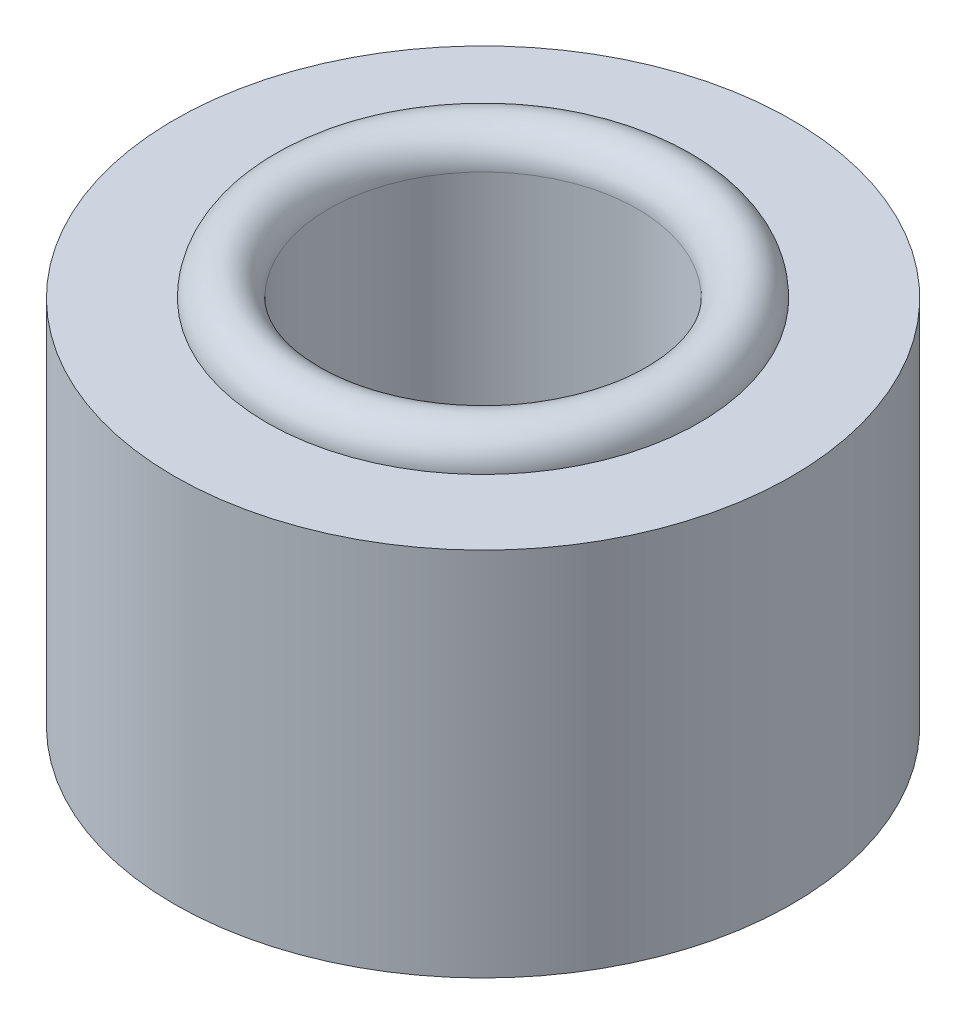
SolidWorks part; units mm, degrees
ref_plane "Front Plane" through (0, 0, 0) normal (0, 0, 1) x (1, 0, 0)
ref_plane "Top Plane" through (0, 0, 0) normal (0, 1, 0) x (1, 0, 0)
ref_plane "Right Plane" through (0, 0, 0) normal (1, 0, 0) x (0, 0, -1)
sketch "Profile Sketch" plane through (0, 0, 0) normal (0, 1, 0) x (1, 0, 0)
  circle A0 centre (0, 0) radius 10
  circle A1 centre (0, 0) radius 5
  dimension "D1" = 20
  dimension "D2" = 10
extrude "Cylinder Extrude" add sketch "Profile Sketch" along normal blind 12
sketch "Lip Ring Sketch" plane through (0, 12, 0) normal (0, 1, 0) x (1, 0, 0)
  circle A0 centre (0, 0) radius 5
  circle A1 centre (0, 0) radius 7
  circle A2 centre (0, 0) radius 5 construction
  dimension "D1" = 2
extrude "Bottom Lip Ring Extrude" add sketch "Lip Ring Sketch" along normal blind 1
fillet "Bottom Ring Fillet" 2 edges at (0, 13, 7) (0, 13, 5) type full round first side face at (0, 13, 7) second side face at (0, 0, 5) middle face at (0, 13, 7)
extrude "Top Lip Ring Extrude" add sketch "Sketch2<2>" against normal blind 1 from surface starting at face at (0, 0, 10)
sketch "Sketch2<2>" plane through (0, 12, 0) normal (0, 1, 0) x (1, 0, 0) same geometry as "Lip Ring Sketch"
fillet "Top Ring Fillet" 2 edges at (0, -1, 7) (0, -1, 5) type full round first side face at (0, -1, 7) second side face at (0, 12, 5) middle face at (0, -1, 5)
